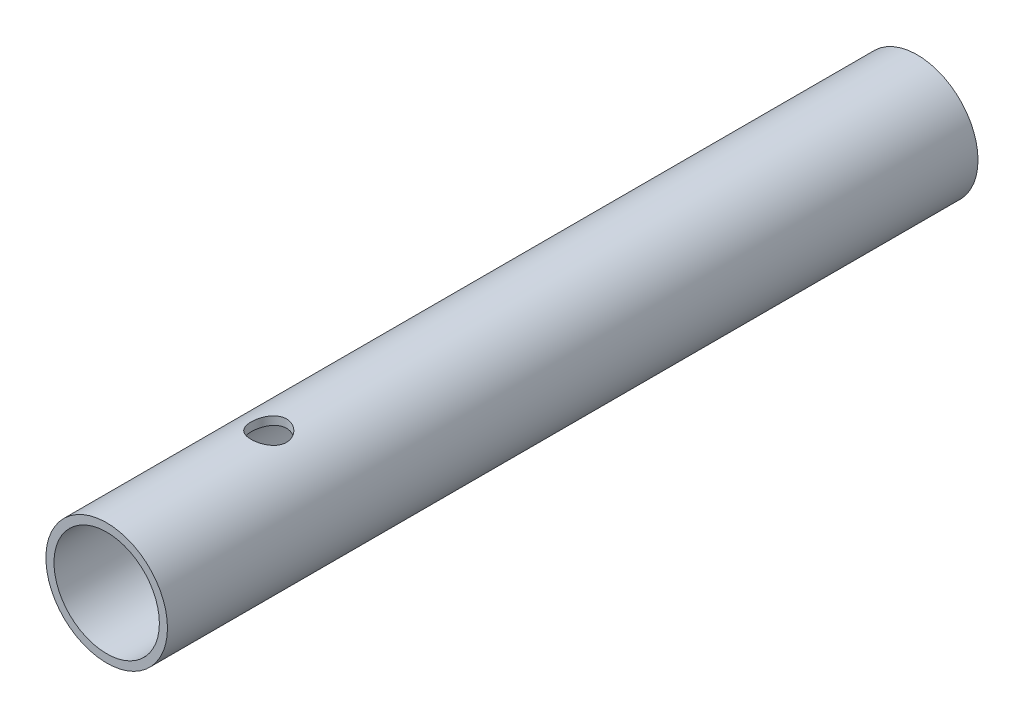
SolidWorks part; units mm, degrees
ref_plane "Front Plane" through (0, 0, 0) normal (0, 0, 1) x (1, 0, 0)
ref_plane "Top Plane" through (0, 0, 0) normal (0, 1, 0) x (1, 0, 0)
ref_plane "Right Plane" through (0, 0, 0) normal (1, 0, 0) x (0, 0, -1)
sketch "Sketch1" plane through (0, 0, 0) normal (0, 0, 1) x (1, 0, 0)
  circle A0 centre (0, 0) radius 19.05
  dimension "D1" = 38.1
extrude "Extrude-Thin1" add sketch "Sketch1" against normal blind 254 thin thin type one direction reverse wall 2.54
sketch "Sketch2" plane through (0, 0, 0) normal (0, 1, 0) x (1, 0, 0)
  line L0 (0, 50.8) -> (0, 0) construction
  circle A0 centre (0, 50.8) radius 5.5563
  dimension "D1" = 11.1125
  dimension "D2" = 50.8
extrude "Cut-Extrude1" cut sketch "Sketch2" along normal through all
